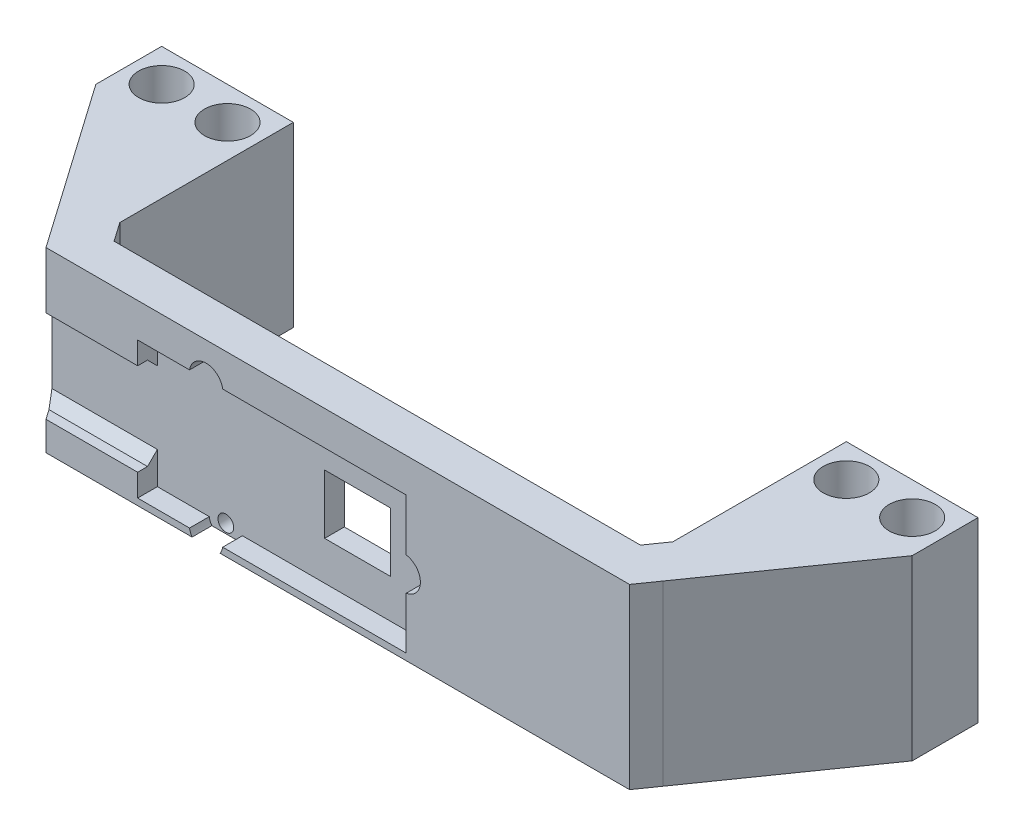
SolidWorks part; units mm, degrees
ref_plane "Front Plane" through (0, 0, 0) normal (0, 0, 1) x (1, 0, 0)
ref_plane "Top Plane" through (0, 0, 0) normal (0, 1, 0) x (1, 0, 0)
ref_plane "Right Plane" through (0, 0, 0) normal (1, 0, 0) x (0, 0, -1)
sketch "Sketch1" plane through (0, 0, 0) normal (0, 1, 0) x (1, 0, 0)
  line L0 (0, 0) -> (0, -3)
  line L1 (0, -3) -> (-46.4204, -3)
  line L2 (-46.4204, -3) -> (-62, 19.25)
  line L3 (-62, 19.25) -> (-62, 29.25)
  line L4 (-62, 29.25) -> (-42, 29.25)
  line L5 (-42, 29.25) -> (-42, 2.8912)
  line L6 (-42, 2.8912) -> (-39.9756, 0)
  line L7 (-39.9756, 0) -> (0, 0)
  line L10 (0, -3) -> (0, 30.804) construction
  line L11 (42, 2.8912) -> (39.9756, 0)
  line L12 (42, 29.25) -> (42, 2.8912)
  line L13 (46.4204, -3) -> (62, 19.25)
  line L14 (62, 19.25) -> (62, 29.25)
  line L15 (62, 29.25) -> (42, 29.25)
  line L16 (39.9756, 0) -> (0, 0)
  line L17 (46.4204, -3) -> (0, -3)
  line L18 (-188, 19.25) -> (62, 19.25) construction
  dimension "D1" = 3
  dimension "D2" = 20
  dimension "D4" = 10
  dimension "D5" = 7
  dimension "D6" = 42
  dimension "D7" = 55
extrude "Boss-Extrude1" add sketch "Sketch1" along normal blind 27 contours L1 L10 L7 L6 L5 L4 L3 L2 | L10 L1 L0 L7 | L17 L13 L14 L15 L12 L11 L16 L0 region at (44.0574, 0, -12.5106) region at (-44.0574, 0, -12.5106)
sketch "Sketch2" plane through (0, 0, 3) normal (0, 0, 1) x (1, 0, 0)
  line L1 (5, 6.9) -> (-5, 6.9)
  line L2 (5, 6.9) -> (5, 15.9)
  line L3 (5, 15.9) -> (-5, 15.9)
  line L4 (-5, 6.9) -> (-5, 15.9)
  line L5 (5, 6.9) -> (-5, 15.9) construction
  line L6 (5, 15.9) -> (-5, 6.9) construction
  point P0 (0, 11.4)
  dimension "D1" = 10
  dimension "D2" = 9
extrude "Cut-Extrude1" cut sketch "Sketch2" against normal through all
hole_wizard "CBORE for M3 Pan Head Screw1" positions "Sketch3" profile "Sketch4" counterbore size "M3" standard "ISO" end condition through all
sketch "Sketch3" plane through (0, 27, 0) normal (0, 1, 0) x (1, 0, 0)
  line L0 (-57, 24.25) -> (-47, 24.25) construction
  line L4 (-62, 19.25) -> (-62, 29.25) construction
  line L6 (-62, 29.25) -> (-42, 29.25) construction
  line L7 (47, 24.25) -> (57, 24.25) construction
  line L8 (62, 19.25) -> (62, 29.25) construction
  line L9 (62, 29.25) -> (42, 29.25) construction
  point P0 (-57, 24.25)
  point P2 (-47, 24.25)
  point P31 (47, 24.25)
  point P32 (57, 24.25)
  dimension "D1" = 10
  dimension "D2" = 5
  dimension "D3" = 5
  dimension "D4" = 10
  dimension "D5" = 5
  dimension "5" = 5
sketch "Sketch4" plane through (-57, 27, -24.25) normal (1, 0, 0) x (0, 0, 1)
  line L0 (0, 0) -> (0, 27)
  line L1 (0, 27) -> (1.7, 27)
  line L3 (1.7, 27) -> (1.7, 8)
  line L4 (1.7, 8) -> (3.5, 8)
  line L5 (3.5, 8) -> (3.5, 0)
  line L7 (3.5, 0) -> (0, 0)
  line L11 (0, -6.35) -> (0, 107.95) construction
  dimension "Thru Hole Dia." = 3.4
  dimension "Thru Hole Depth" = 27
  dimension "C'Bore Dia." = 7
  dimension "C'Bore Depth" = 8
hole_wizard "CSK for M2 Countersunk Flat Head Screw1" positions "Sketch5" profile "Sketch6" countersink size "M2" standard "ISO" end condition through all
sketch "Sketch5" plane through (0, 0, 0) normal (0, 0, 1) x (1, 0, 0)
  point P0 (-20, 21.4)
  point P3 (-20, 1.4)
  point P6 (10, 11.4)
sketch "Sketch6" plane through (-20, 21.4, 0) normal (1, 0, 0) x (0, 1, 0)
  line L0 (0, 0) -> (0, 3)
  line L1 (0, 3) -> (1.2, 3)
  line L2 (1.2, 3) -> (1.2, 1)
  line L3 (1.2, 1) -> (2.2, 0)
  line L5 (2.2, 0) -> (0, 0)
  line L6 (-1.2, 1) -> (-2.2, 0) construction
  line L11 (0, -6.35) -> (0, 107.95) construction
  dimension "Thru Hole Dia." = 2.4
  dimension "Thru Hole Depth" = 3
  dimension "Near C'Sink Dia." = 4.4
  dimension "Near C'Sink Angle" = 90
sketch "Sketch7" plane through (0, 0, 3) normal (0, 0, 1) x (1, 0, 0)
  line L0 (-30.4, 21.8) -> (-30.4, 1)
  line L1 (-46.4204, 27) -> (46.4204, 27)
  line L2 (-46.4204, 27) -> (-46.4204, 0)
  line L3 (-46.4204, 0) -> (46.4204, 0)
  line L4 (46.4204, 27) -> (46.4204, 0)
  line L5 (-29.2, 20.6) -> (9.2, 20.6)
  line L6 (-29.2, 20.6) -> (-29.2, 2.2)
  line L7 (-29.2, 2.2) -> (9.2, 2.2)
  line L8 (9.2, 20.6) -> (9.2, 2.2)
  line L9 (-30.4, 1) -> (10.4, 1)
  line L10 (10.4, 21.8) -> (10.4, 1)
  line L11 (-30.4, 21.8) -> (10.4, 21.8)
  line L12 (-30.4, 4.4) -> (-46.4204, 18.4) construction
  line L13 (-30.4, 4.4) -> (-46.4204, 4.4)
  line L14 (-30.4, 4.4) -> (-30.4, 18.4)
  line L15 (-30.4, 18.4) -> (-46.4204, 18.4)
  line L16 (-46.4204, 4.4) -> (-46.4204, 18.4)
  circle A0 centre (-20, 21.4) radius 2.55
  circle A1 centre (-20, 21.4) radius 1.2 construction
  circle A2 centre (-20, 1.4) radius 2.55
  circle A3 centre (10, 11.4) radius 2.55
  circle A4 centre (-20, 1.4) radius 1.2 construction
  circle A5 centre (10, 11.4) radius 1.2 construction
  point P29 (-30.4, 11.4)
  point P30 (-38.4102, 11.4)
  point P31 (0, 0)
  point P32 (0, 0)
  point P35 (0, 0)
  point P38 (0, 0)
  line M14 (-46.4204, 0) -> (46.4204, 0)
  line M15 (46.4204, 0) -> (46.4204, 27)
  line M16 (46.4204, 27) -> (-46.4204, 27)
  line M17 (-46.4204, 27) -> (-46.4204, 0)
  dimension "D2" = 5.1
  dimension "D3" = 5.1
  dimension "D4" = 5.1
  dimension "D5" = 14
  dimension "D1" = 1.2
extrude "Boss-Extrude2" add sketch "Sketch7" along normal blind 3 contours A3 L10 L9 A2 L15 L0 L11 A0 M14 M15 M16 M17 | A2 L9 L0 L13 L2 M14 region at (15.1306, 15.8667, 3) region at (-37.1795, 2.0257, 3)
chamfer "Chamfer1" distance 1.5 angle 45 2 edges at (-38.4102, 4.4, 3) (-38.4102, 18.4, 3)
chamfer "Chamfer2" distance 3 angle 35 3 edges at (46.4204, 13.5, 6) (-46.4204, 2.2, 6) (-46.4204, 22.7, 6) first distance on face at (46.4204, 13.5, 4.5) first distance on face at (-46.4204, 2.94, 4.5) first distance on face at (-46.4204, 21.54, 4.5)
